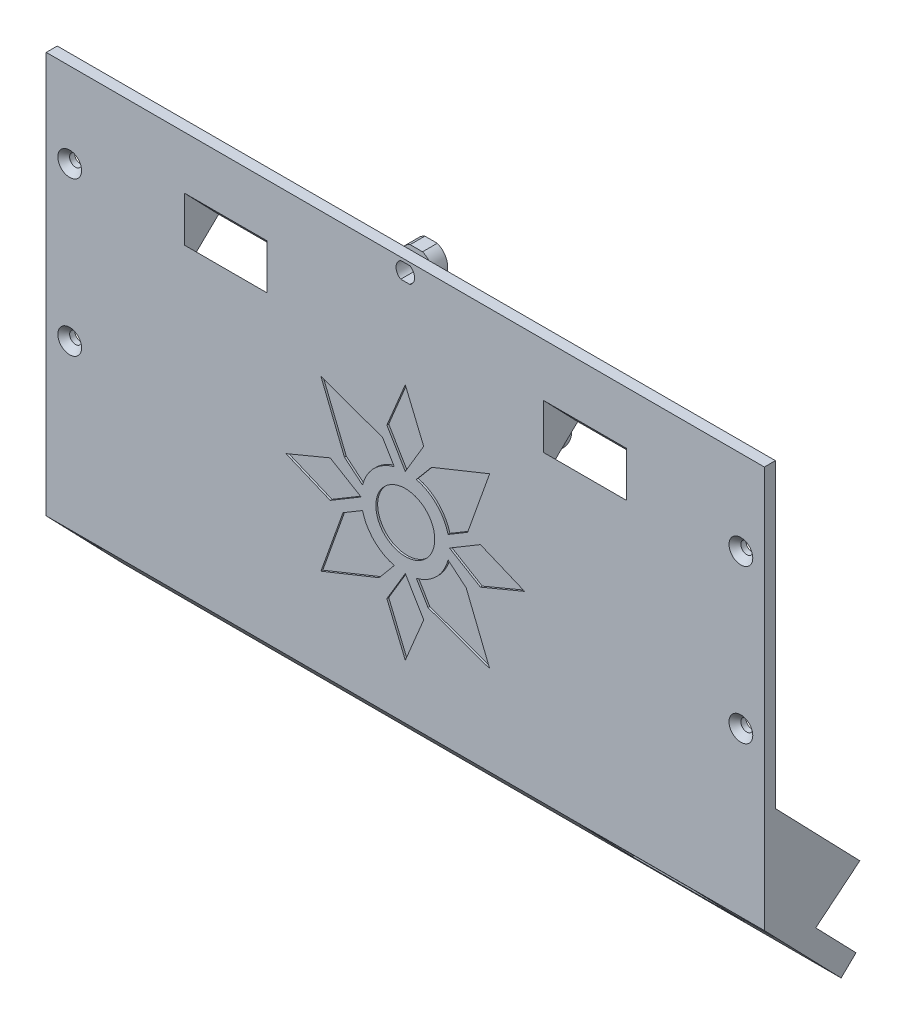
SolidWorks part; units mm, degrees
ref_plane "Alzado" through (0, 0, 0) normal (0, 0, 1) x (1, 0, 0)
ref_plane "Planta" through (0, 0, 0) normal (0, 1, 0) x (1, 0, 0)
ref_plane "Vista lateral" through (0, 0, 0) normal (1, 0, 0) x (0, 0, -1)
sketch "Croquis1" plane through (0, 0, 0) normal (0, 0, 1) x (1, 0, 0)
  line L0 (-97.5, 0) -> (97.5, 0)
  line L1 (97.5, 0) -> (97.5, 38)
  line L2 (97.5, 38) -> (-97.5, 38)
  line L3 (0, 0) -> (0, 28.0598) construction
  line L4 (-97.5, 0) -> (-97.5, 38)
  circle A2 centre (91.125, 15) radius 1.625
  circle A3 centre (-91.125, 15) radius 1.625
  point P13 (0, 38)
  point P14 (0, 0)
  dimension "D1" = 3.25
  dimension "D2" = 15
  dimension "D3" = 97.5
  dimension "D4" = 38
  dimension "D5" = 6.375
extrude "Saliente-Extruir1" add sketch "Croquis1" along normal blind 3
sketch "Croquis8" plane through (0, 0, 0) normal (0, -1, 0) x (1, 0, 0)
  line L1 (-97.5, 3) -> (97.5, 3)
  line L2 (-97.5, 3) -> (-97.5, 0)
  line L3 (-97.5, 0) -> (97.5, 0)
  line L4 (97.5, 3) -> (97.5, 0)
extrude "Saliente-Extruir5" add sketch "Croquis8" along normal blind 5
sketch "Croquis9" plane through (0, 38, 0) normal (0, 1, 0) x (1, 0, 0)
  line L1 (-97.5, 0) -> (97.5, 0)
  line L2 (-97.5, 0) -> (-97.5, -3)
  line L3 (-97.5, -3) -> (97.5, -3)
  line L4 (97.5, 0) -> (97.5, -3)
extrude "Saliente-Extruir6" add sketch "Croquis9" along normal blind 5
sketch "Croquis10" plane through (97.5, 0, 0) normal (1, 0, 0) x (0, 0, -1)
  line L0 (0, 35.8022) -> (10.5168, 24.9118)
  line L1 (1.1653, 15.8812) -> (0, 14.7559)
  line L2 (0, 35.8022) -> (0, 14.7559)
  line L3 (0, -5) -> (0, 43) construction
  line L4 (10.5168, 24.9118) -> (1.1653, 15.8812)
  line L6 (-3, 20.8949) -> (0, 17.7883) construction
  line L7 (-3, -5) -> (-3, 43) construction
  line L8 (-3, 20.8949) -> (4.7747, 28.4028) construction
  dimension "D1" = 5
  dimension "D2" = 6.5
  dimension "D3" = 14.62
  dimension "D4" = 44
extrude "Saliente-Extruir7" add sketch "Croquis10" against normal blind 35 from offset 35 offset against normal yes
sketch "Croquis11" plane through (0, 7.6354, 7.3734) normal (0, -0.7193, -0.6947) x (1, 0, 0)
  line L3 (60, -15.3703) -> (37.5, -15.3703)
  line L6 (37.5, -15.3703) -> (37.5, -23.8703)
  line L7 (37.5, -23.8703) -> (60, -23.8703)
  line L8 (60, -23.8703) -> (60, -15.3703)
  line L9 (62.5, -10.2503) -> (62.5, -24.8703) construction
  line L10 (27.5, -24.8703) -> (62.5, -24.8703) construction
  dimension "D1" = 8.5
  dimension "D2" = 22.5
  dimension "D3" = 2.5
  dimension "D4" = 1
extrude "Cortar-Extruir4" cut sketch "Croquis11" against normal through all both and the other way through all
sketch "Croquis12" plane through (62.5, 0, 0) normal (1, 0, 0) x (0, 0, -1)
  line L0 (10.5168, 24.9118) -> (0, 14.7559)
  line L1 (0, 14.7559) -> (0, 21.7067)
  line L2 (0, -5) -> (0, 43) construction
  line L3 (0, 21.7067) -> (7.0435, 28.5085)
  line L4 (10.5168, 24.9118) -> (0, 35.8022) construction
  line L5 (7.0435, 28.5085) -> (10.5168, 24.9118)
  dimension "D1" = 5
extrude "Cortar-Extruir5" cut sketch "Croquis12" against normal up to next
sketch "Croquis13" plane through (0, 11.2321, 10.8467) normal (0, -0.7193, -0.6947) x (1, 0, 0)
  line L0 (27.5, -15.0787) -> (27.5, -24.8703) construction
  line L3 (27.5, -24.8703) -> (62.5, -24.8703) construction
  circle A0 centre (33.75, -19.7103) radius 1
  dimension "D1" = 2
  dimension "D3" = 5.16
  dimension "D2" = 6.25
extrude "Cortar-Extruir6" cut sketch "Croquis13" against normal blind 5
sketch "Croquis14" plane through (-97.5, 0, 0) normal (-1, 0, 0) x (0, 0, 1)
  line L0 (0, 21.7067) -> (-7.0435, 28.5085)
  line L1 (-7.0435, 28.5085) -> (0, 35.8022)
  line L2 (0, 35.8022) -> (0, 21.7067)
extrude "Saliente-Extruir8" add sketch "Croquis14" against normal blind 35 from offset 35 offset against normal yes
sketch "Croquis16" plane through (0, 11.2321, 10.8467) normal (0, -0.7193, -0.6947) x (1, 0, 0)
  line L0 (0, 0) -> (0, -29.2293) construction
  line L5 (-37.5, -23.8703) -> (-60, -23.8703)
  line L6 (-60, -15.3703) -> (-60, -23.8703)
  line L8 (-37.5, -15.3703) -> (-60, -15.3703)
  line L9 (60, -23.8703) -> (37.5, -23.8703) construction
  line L10 (-37.5, -15.3703) -> (-37.5, -23.8703)
  line L11 (-62.5, -24.8703) -> (-62.5, -15.0787) construction
  line L12 (37.5, -15.3703) -> (60, -15.3703) construction
  dimension "D1" = 22.5
  dimension "D2" = 2.5
extrude "Cortar-Extruir7" cut sketch "Croquis16" against normal through all both and the other way through all
sketch "Croquis17" plane through (0, 11.2321, 10.8467) normal (0, -0.7193, -0.6947) x (1, 0, 0)
  line L0 (0, 0) -> (0, -24) construction
  line L1 (-27.5, -24.8703) -> (-62.5, -24.8703) construction
  line L3 (-37.5, -23.8703) -> (-37.5, -15.3703) construction
  circle A1 centre (-33.75, -19.7103) radius 1
  dimension "D1" = 5.16
  dimension "D2" = 3.75
extrude "Cortar-Extruir8" cut sketch "Croquis17" against normal blind 5
sketch "Croquis18" plane through (0, 0, 3) normal (0, 0, 1) x (1, 0, 0)
  line L0 (-97.5, 19) -> (97.5, 19) construction
  circle A2 centre (91.125, 23) radius 1.625
  circle A3 centre (-91.125, 23) radius 1.625
extrude "Cortar-Extruir9" cut sketch "Croquis18" against normal blind 10
sketch "Croquis19" plane through (0, 0, 3) normal (0, 0, 1) x (1, 0, 0)
  line L0 (-97.5, 43) -> (-97.5, -5) construction
  line L1 (-97.5, 19) -> (97.5, 19)
  line L2 (-97.5, 19) -> (-97.5, -5)
  line L3 (-97.5, -5) -> (97.5, -5)
  line L4 (97.5, 19) -> (97.5, -5)
extrude "Saliente-Extruir9" add sketch "Croquis19" against normal up to vertex (3 mm away) up to point (-97.5, -5, 0)
sketch "Croquis20" plane through (0, 0, 3) normal (0, 0, 1) x (1, 0, 0)
  line L0 (-97.5, 43) -> (97.5, 43) construction
  line L1 (-97.5, -5) -> (97.5, -5)
  line L2 (-97.5, -5) -> (-97.5, -33.69)
  line L3 (-97.5, -33.69) -> (97.5, -33.69)
  line L4 (97.5, -5) -> (97.5, -33.69)
  dimension "D1" = 76.69
extrude "Saliente-Extruir10" add sketch "Croquis20" against normal up to vertex (3 mm away) up to point (-97.5, -5, 0)
sketch "Croquis22" plane through (0, 0, 3) normal (0, 0, 1) x (1, 0, 0)
  line L0 (-97.5, 43) -> (-97.5, -33.69) construction
  line L1 (-97.5, 43) -> (97.5, 43)
  line L2 (-97.5, 43) -> (-97.5, 51.7993)
  line L3 (-97.5, 51.7993) -> (97.5, 51.7993)
  line L4 (97.5, 43) -> (97.5, 51.7993)
  line L5 (-97.5, 27.545) -> (-86.6825, 27.545)
  line L6 (-97.5, 27.545) -> (-97.5, 18.136)
  line L7 (-97.5, 18.136) -> (-86.6825, 18.136)
  line L8 (-86.6825, 27.545) -> (-86.6825, 18.136)
  line L9 (97.5, -33.69) -> (97.5, 43) construction
  line L10 (86.4429, 27.545) -> (97.5, 27.545)
  line L11 (86.4429, 27.545) -> (86.4429, 18.136)
  line L12 (86.4429, 18.136) -> (97.5, 18.136)
  line L13 (97.5, 27.545) -> (97.5, 18.136)
extrude "Saliente-Extruir11" add sketch "Croquis22" against normal up to vertex (3 mm away) up to point (-97.5, -33.69, 0)
sketch "Croquis23" plane through (0, 0, 3) normal (0, 0, 1) x (1, 0, 0)
  line L1 (-97.5, 51.7993) -> (-97.5, -33.69) construction
  line L2 (97.5, 51.7993) -> (-97.5, 51.7993) construction
  line L3 (0, -1.1555) -> (0, 35.7449) construction
  circle A0 centre (-91.125, 28.7993) radius 1.625
  circle A1 centre (-91.125, -12.8907) radius 1.625
  circle A2 centre (91.125, -12.8907) radius 1.625
  circle A3 centre (91.125, 28.7993) radius 1.625
  dimension "D1" = 6.375
  dimension "D2" = 23
  dimension "D3" = 41.69
  dimension "D4" = 3.25
extrude "Cortar-Extruir10" cut sketch "Croquis23" against normal blind 10
sketch "Croquis25" plane through (-97.5, 0, 0) normal (-1, 0, 0) x (0, 0, 1)
  line L0 (0, 51.7993) -> (0, -33.69) construction
  line L1 (0, -27.2007) -> (6.0483, -27.2007)
  line L2 (0, -27.2007) -> (0, -41.7759)
  line L3 (0, -41.7759) -> (6.0483, -41.7759)
  line L4 (6.0483, -27.2007) -> (6.0483, -41.7759)
  line L5 (0, 51.7993) -> (3, 51.7993) construction
  dimension "D1" = 79
extrude "Cortar-Extruir11" cut sketch "Croquis25" against normal through all both and the other way through all
sketch "Croquis29" plane through (97.5, 0, 0) normal (1, 0, 0) x (0, 0, -1)
  line L0 (-3, -27.2007) -> (22.7607, -53.8767)
  line L1 (-3, -27.2007) -> (-2.8548, -27.0605)
  line L2 (22.7607, -53.8767) -> (22.9059, -53.7364)
  line L3 (-2.8548, -27.0605) -> (22.9059, -53.7364)
  line L4 (7.0435, 28.5085) -> (0, 35.8022) construction
  dimension "D1" = 35
extrude "Saliente-Extruir15" add sketch "Croquis29" against normal blind 12.75
sketch "Croquis30" plane through (-97.5, 0, 0) normal (-1, 0, 0) x (0, 0, 1)
  line L0 (0, -27.2007) -> (3, -27.2007)
  line L1 (3, -27.2007) -> (-22.7607, -53.8767)
  line L2 (-22.7607, -53.8767) -> (-22.9059, -53.7364)
  line L3 (-22.9059, -53.7364) -> (0, -27.2007)
extrude "Saliente-Extruir16" add sketch "Croquis30" against normal blind 12.75
sketch "Croquis27" plane through (97.5, 0, 0) normal (1, 0, 0) x (0, 0, -1)
  line L1 (-3, -27.2007) -> (0, -27.2007)
  line L2 (-3, -27.2007) -> (-3, -57.2007)
  line L3 (-3, -57.2007) -> (0, -57.2007)
  line L4 (0, -27.2007) -> (0, -57.2007)
  dimension "D1" = 30
extrude "Saliente-Extruir13" add sketch "Croquis27" against normal blind 195
sketch "Croquis28" plane through (97.5, 0, 0) normal (1, 0, 0) x (0, 0, -1)
  line L0 (0, -52.2007) -> (21.8906, -74.8691)
  line L1 (0, -52.2007) -> (-3, -55.0978)
  line L2 (21.8906, -74.8691) -> (16.2585, -80.3079)
  line L4 (0, -57.2007) -> (0, -30.3073) construction
  line L5 (7.0435, 28.5085) -> (0, 35.8022) construction
  line L6 (-3, -57.2007) -> (0, -57.2007) construction
  line L7 (-3, -57.2007) -> (17.8398, -78.7809)
  line L8 (-3, -55.0978) -> (-3, -57.2007)
  line L9 (-3, -57.2007) -> (-3, 51.7993) construction
  line M6 (-3, 51.7993) -> (-3, -57.2007)
  line M7 (-3, -57.2007) -> (0, -57.2007)
  line M8 (0, -57.2007) -> (0, -30.3073)
  dimension "D1" = 5
  dimension "D2" = 30
extrude "Saliente-Extruir14" add sketch "Croquis28" against normal blind 195 contours L7 L2 L0 M7 M8 | L1 M8 M6 M7 region at (97.5, -55.3265, 1.2961) region at (97.5, -66.2068, -9.6586)
sketch "Croquis31" plane through (0, -14.6248, 15.1444) normal (0, -0.6947, 0.7193) x (1, 0, 0)
  line L1 (0, 0) -> (0, -106.5046) construction
  line L2 (97.5, -21.5922) -> (84.75, -21.5922) construction
  circle A0 centre (91.125, -45.0422) radius 1.625
  circle A1 centre (-91.125, -45.0422) radius 1.625
  dimension "D1" = 3.25
  dimension "D2" = 23.45
extrude "Cortar-Extruir12" cut sketch "Croquis31" against normal through all both and the other way through all
sketch "Croquis32" plane through (97.5, 0, 0) normal (1, 0, 0) x (0, 0, -1)
  line L0 (0, -30.3073) -> (22.7607, -53.8767)
  line L1 (22.7607, -53.8767) -> (10.9453, -63.5349)
  line L2 (0, -52.2007) -> (21.8906, -74.8691) construction
  line L3 (10.9453, -63.5349) -> (0, -52.2007)
  line L4 (0, -52.2007) -> (0, -30.3073)
extrude "Saliente-Extruir17" add sketch "Croquis32" against normal blind 12.75
sketch "Croquis33" plane through (-97.5, 0, 0) normal (-1, 0, 0) x (0, 0, 1)
  line L0 (0, -30.3073) -> (0, -52.2007)
  line L1 (0, -52.2007) -> (-10.9453, -63.5349)
  line L2 (-10.9453, -63.5349) -> (-22.7607, -53.8767)
  line L3 (-22.7607, -53.8767) -> (0, -30.3073)
extrude "Saliente-Extruir18" add sketch "Croquis33" against normal blind 12.75
sketch "Croquis39" plane through (0, -14.4845, 14.9992) normal (0, 0.6947, -0.7193) x (-1, 0, 0)
  circle A0 centre (91.125, -45.0422) radius 1.625
  circle A1 centre (-91.125, -45.0422) radius 1.625
extrude "Cortar-Extruir15" cut sketch "Croquis39" against normal through all both and the other way through all
sketch "Croquis40" plane through (0, -14.4845, 14.9992) normal (0, 0.6947, -0.7193) x (-1, 0, 0)
  circle A0 centre (-91.125, -45.0422) radius 4
  circle A1 centre (91.125, -45.0422) radius 4
  dimension "D1" = 8
  dimension "D2" = 8
extrude "Cortar-Extruir16" cut sketch "Croquis40" against normal through all from offset 4 offset against normal yes
sketch "Croquis43" plane through (0, -49.6796, -47.975) normal (0, -0.7193, -0.6947) x (1, 0, 0)
  line L0 (-97.5, 36.2617) -> (97.5, 36.2617) construction
  line L1 (-10, 36.2617) -> (10, 36.2617)
  line L2 (-10, 36.2617) -> (-10, 26.2617)
  line L3 (-10, 26.2617) -> (-3.75, 26.2617)
  line L4 (10, 36.2617) -> (10, 26.2617)
  line L5 (-3.75, 31.2617) -> (-3.75, 26.2617)
  line L7 (3.75, 26.2617) -> (3.75, 31.2617)
  line L8 (3.75, 26.2617) -> (10, 26.2617)
  arc A0 (3.75, 31.2617) -> (-3.75, 31.2617) centre (0, 31.2617) ccw
  dimension "D4" = 7.5
  dimension "D5" = 5
  dimension "D1" = 10
  dimension "D2" = 20
  dimension "D3" = 10
extrude "Saliente-Extruir19" add sketch "Croquis43" against normal blind 4 from offset 15 offset against normal yes
chamfer "Chaflán1" distance 10 angle 45 2 edges at (-10, -62.6403, -10.0814) (10, -62.6403, -10.0814)
sketch "Croquis44" plane through (-97.5, 0, 0) normal (-1, 0, 0) x (0, 0, 1)
  line L5 (-30.1807, -62.0253) -> (-19.473, -72.3656)
  line L6 (-10.9453, -63.5349) -> (-21.8906, -74.8691) construction
  line L7 (-19.473, -72.3656) -> (-10.9453, -63.5349)
  line L8 (-10.9453, -63.5349) -> (-22.9059, -53.7364)
  line L9 (-22.9059, -53.7364) -> (-30.1807, -62.0253)
  dimension "D1" = 43.9904
extrude "Saliente-Extruir20" add sketch "Croquis44" against normal blind 3
sketch "Croquis47" plane through (0, -29.1013, 30.1353) normal (0, -0.6947, 0.7193) x (1, 0, 0)
  line L0 (-97.5, -39.0628) -> (97.5, -39.0628) construction
  line L1 (48.7328, -44.0628) -> (73.7328, -44.0628)
  line L2 (48.7328, -44.0628) -> (48.7328, -59.0628)
  line L3 (48.7328, -59.0628) -> (73.7328, -59.0628)
  line L4 (73.7328, -44.0628) -> (73.7328, -59.0628)
  dimension "D1" = 15
  dimension "D2" = 25
  dimension "D3" = 5
extrude "Cortar-Extruir17" cut sketch "Croquis47" against normal up to next
sketch "Croquis48" plane through (0, 0, 3) normal (0, 0, 1) x (1, 0, 0)
  line L0 (97.5, 51.7993) -> (-97.5, 51.7993) construction
  line L2 (-1.2392, 50.9993) -> (1.2392, 50.9993)
  line L4 (1.2392, 46.5993) -> (-1.2392, 46.5993)
  arc A0 (-2.2, 47.5601) -> (-1.2392, 46.5993) centre (0, 48.7993) ccw construction
  arc A2 (-2.2, 47.5601) -> (-1.2392, 46.5993) centre (0, 48.7993) ccw
  arc A3 (-1.2392, 50.9993) -> (-1.2392, 46.5993) centre (0, 48.7993) ccw
  arc A4 (1.2392, 46.5993) -> (1.2392, 50.9993) centre (0, 48.7993) ccw
  dimension "D2" = 5.05
  dimension "D1" = 3
  dimension "D3" = 2.2
  dimension "D4" = 2.2
extrude "Cortar-Extruir18" cut sketch "Croquis48" against normal up to next contours L4 A4 L2 A3 A2 region at (0, 48.7993, 3)
sketch "Croquis49" plane through (0, 0, 3) normal (0, 0, 1) x (1, 0, 0)
  line L2 (0, -10) -> (0, 0) construction
  line L20 (0, 2) -> (-5, 10.3961)
  line L21 (-5, 10.3961) -> (0, 22.3961)
  line L36 (5, 10.3961) -> (0, 22.3961)
  line L37 (0, 2) -> (5, 10.3961)
  line L50 (-6.1541, 6.9153) -> (-3, 1.619)
  line L51 (-16.5376, -2.8931) -> (-11.619, -7)
  line L52 (-11.619, -7) -> (-3, 1.619) construction
  line L53 (0, -10) -> (-22.9075, 12.9075) construction
  line L54 (-16.5376, -2.8931) -> (-22.9075, 12.9075)
  line L55 (-22.9075, 12.9075) -> (-6.1541, 6.9153)
  line L56 (12, -10) -> (20.3961, -15)
  line L57 (12, -10) -> (20.3961, -5)
  line L58 (20.3961, -5) -> (32.3961, -10)
  line L59 (20.3961, -15) -> (32.3961, -10)
  line L60 (0, -22) -> (-5, -30.3961)
  line L61 (0, -22) -> (5, -30.3961)
  line L62 (5, -30.3961) -> (0, -42.3961)
  line L63 (-5, -30.3961) -> (0, -42.3961)
  line L64 (-12, -10) -> (-20.3961, -5)
  line L65 (-12, -10) -> (-20.3961, -15)
  line L66 (-20.3961, -15) -> (-32.3961, -10)
  line L67 (-20.3961, -5) -> (-32.3961, -10)
  line L68 (0, -10) -> (0, 2) construction
  line L69 (7.1069, 6.5376) -> (3, 1.619)
  line L70 (7.1069, 6.5376) -> (22.9075, 12.9075)
  line L71 (22.9075, 12.9075) -> (16.9153, -3.8459)
  line L72 (16.9153, -3.8459) -> (11.619, -7)
  line L73 (16.5376, -17.1069) -> (11.619, -13)
  line L74 (16.5376, -17.1069) -> (22.9075, -32.9075)
  line L75 (22.9075, -32.9075) -> (6.1541, -26.9153)
  line L76 (6.1541, -26.9153) -> (3, -21.619)
  line L77 (-7.1069, -26.5376) -> (-3, -21.619)
  line L78 (-7.1069, -26.5376) -> (-22.9075, -32.9075)
  line L79 (-22.9075, -32.9075) -> (-16.9153, -16.1541)
  line L80 (-16.9153, -16.1541) -> (-11.619, -13)
  line L81 (0, -10) -> (-3, 1.619) construction
  circle A8 centre (0, -10) radius 8
  circle A9 centre (0, -10) radius 18 construction
  circle A10 centre (0, -10) radius 21 construction
  circle A11 centre (0, -10) radius 12
  circle A12 centre (0, -10) radius 32.3961 construction
  dimension "D1" = 16
  dimension "D2" = 4
  dimension "D3" = 6
  dimension "D4" = 3
  dimension "D10" = 12
  dimension "D5" = 10
  dimension "D6" = 12
  dimension "D7" = 5
  dimension "D9" = 3
  dimension "D11" = 3
  dimension "D12" = 11.619
  dimension "D13" = 4
  dimension "D14" = 12
  dimension "D8" = 4
extrude "Cortar-Extruir19" cut sketch "Croquis49" against normal blind 0.5 contours A11 L50 L55 L54 L51 | L20 L37 L36 L21 | A11 L72 L71 L70 L69 | L56 L59 L58 L57 | A11 L76 L75 L74 L73 | A8 | L60 L63 L62 L61 | A11 L80 L79 L78 L77 | L64 L67 L66 L65
chamfer "Chaflán2" distance 3 angle 45 4 edges at (73.7328, -66.1925, -5.6832) (61.2328, -60.7974, -0.4733) (48.7328, -66.1925, -5.6832) (61.2328, -71.5875, -10.8932)
sketch "Croquis51" plane through (0, 0, 0) normal (0, 0, -1) x (-1, 0, 0)
  line L10 (-1.6839, 44.5993) -> (1.6839, 44.5993)
  line L11 (1.6839, 52.9993) -> (-1.6839, 52.9993)
  line L12 (-1.6839, 44.5993) -> (1.6839, 44.5993)
  line L13 (1.6839, 52.9993) -> (-1.6839, 52.9993)
  line L16 (-1.2392, 46.5993) -> (1.2392, 46.5993)
  line L17 (1.2392, 50.9993) -> (-1.2392, 50.9993)
  line L18 (-1.2392, 46.5993) -> (1.2392, 46.5993)
  line L19 (1.2392, 50.9993) -> (-1.2392, 50.9993)
  arc A10 (-1.6839, 52.9993) -> (-1.6839, 44.5993) centre (0, 48.7993) ccw
  arc A11 (1.6839, 44.5993) -> (1.6839, 52.9993) centre (0, 48.7993) ccw
  arc A12 (-1.6839, 52.9993) -> (-1.6839, 44.5993) centre (0, 48.7993) ccw
  arc A13 (1.6839, 44.5993) -> (1.6839, 52.9993) centre (0, 48.7993) ccw
  arc A16 (1.2392, 46.5993) -> (1.2392, 50.9993) centre (0, 48.7993) ccw
  arc A17 (-1.2392, 50.9993) -> (-1.2392, 46.5993) centre (0, 48.7993) ccw
  arc A18 (1.2392, 46.5993) -> (1.2392, 50.9993) centre (0, 48.7993) ccw
  arc A19 (-1.2392, 50.9993) -> (-1.2392, 46.5993) centre (0, 48.7993) ccw
  dimension "D1" = 2
  dimension "D2" = 0
extrude "Saliente-Extruir22" add sketch "Croquis51" along normal blind 4
chamfer "Chaflán3" distance 1.6 angle 45 4 edges at (-89.5, -12.8907, 3) (-89.5, 28.7993, 3) (89.5, -12.8907, 3) (89.5, 28.7993, 3)
sketch "Croquis52" plane through (0, 11.2321, 10.8467) normal (0, -0.7193, -0.6947) x (1, 0, 0)
  line L0 (0, 0) -> (0, -21.985) construction
  circle A0 centre (33.75, -19.7103) radius 1
  circle A1 centre (33.75, -19.7103) radius 3
  circle A2 centre (-33.75, -19.7103) radius 1
  circle A3 centre (-33.75, -19.7103) radius 3
  dimension "D1" = 2
extrude "Saliente-Extruir23" add sketch "Croquis52" along normal blind 2
